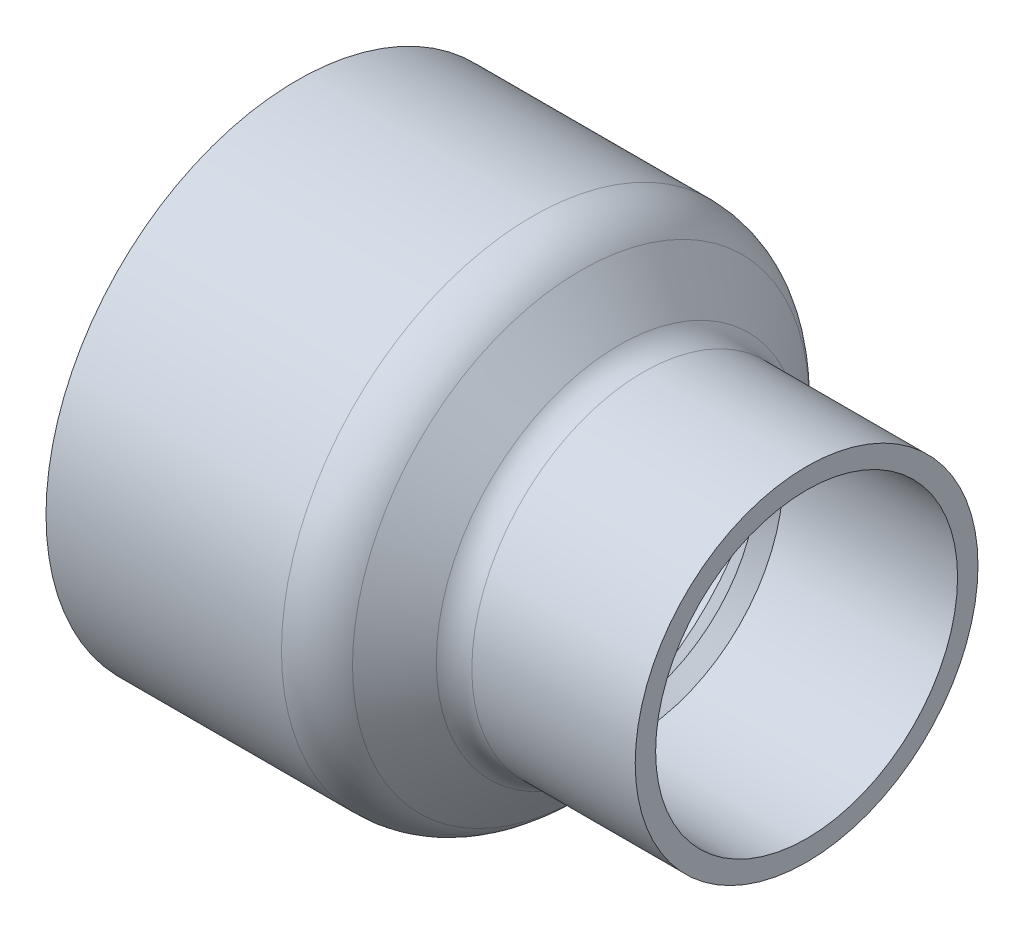
SolidWorks part; units mm, degrees
ref_plane "Front Plane" through (0, 0, 0) normal (0, 0, 1) x (1, 0, 0)
ref_plane "Top Plane" through (0, 0, 0) normal (0, 1, 0) x (1, 0, 0)
ref_plane "Right Plane" through (0, 0, 0) normal (1, 0, 0) x (0, 0, -1)
sketch "Sketch0" plane through (0, 0, 0) normal (0, 0, 1) x (1, 0, 0)
  line L0 (-51.181, 0) -> (16.383, 0) construction
  line L2 (-0.381, 0) -> (16.383, 0) construction
  line L3 (-51.181, 0) -> (51.181, 0) construction
  line L4 (-51.181, 50.3682) -> (-51.181, -50.3682) construction
  line L5 (-0.381, 44.3484) -> (-51.181, 44.6532) construction
  line L6 (-0.381, 44.3484) -> (-0.381, -44.3484) construction
  line L7 (-0.381, -44.3484) -> (-51.181, -44.6532) construction
  line L8 (-51.181, 44.6532) -> (-51.181, -44.6532) construction
  line L9 (51.181, 30.3149) -> (51.181, -30.3149) construction
  line L10 (51.181, 34.417) -> (51.181, -34.417) construction
  line L11 (16.383, 26.2509) -> (16.383, -26.2509) construction
  line L12 (16.383, 30.0863) -> (16.383, -30.0863) construction
  line L13 (16.383, -30.0863) -> (51.181, -30.3149) construction
  line L14 (-0.381, 38.9636) -> (-0.381, -38.9636) construction
  line L15 (16.383, 30.0863) -> (51.181, 30.3149) construction
  dimension "N" = 16.764
  dimension "M" = 100.7364
  dimension "OD A" = 89.3064
  dimension "OD B" = 88.6968
  dimension "ID" = 77.9272
  dimension "L" = 102.362
  dimension "ID2" = 52.5018
  dimension "OD B2" = 60.1726
  dimension "OD A2" = 60.6298
  dimension "M2" = 68.834
  dimension "C" = 50.8
  dimension "C2" = 34.798
sketch "Sketch1" plane through (0, 0, 0) normal (0, 0, 1) x (1, 0, 0)
  line L0 (-51.181, 0) -> (16.383, 0) construction
  line L1 (-51.181, 0) -> (16.383, 0) construction
  line L2 (-0.381, -44.3484) -> (13.5682, -27.7244)
  line L3 (0, -52.7853) -> (-4.3779, -49.1118) construction
  line L4 (-51.181, -50.3682) -> (-51.181, -44.6532)
  line L5 (-51.181, -44.6532) -> (-0.381, -44.3484)
  line L7 (13.5682, -27.7244) -> (16.383, -30.0863)
  line L8 (2.0282, -50.3682) -> (15.4128, -34.417)
  line L9 (2.0282, -50.3682) -> (-51.181, -50.3682)
  line L10 (0, 0) -> (0, -52.7853) construction
  line L12 (16.383, -30.0863) -> (51.181, -30.3149)
  line L13 (51.181, -30.3149) -> (51.181, -34.417)
  line L14 (51.181, -34.417) -> (15.4128, -34.417)
  dimension "D1" = 40
revolve "Revolve1" add sketch "Sketch1" angle 360 about L1
fillet "Fillet1" radius 12.7 1 edges at (2.0282, 0, 50.3682)
fillet "Fillet2" radius 6.35 1 edges at (15.4128, 0, 34.417)
other "CPoint1" parameters "Diameter"=50.8, "StubLength"=152.4
ref_axis "Axis1" through (26.383, 0, 0) along (-1, 0, 0)
other "CPoint2" parameters "Diameter"=76.2, "StubLength"=76.2
ref_axis "Axis2" through (-10.381, 0, 0) along (1, 0, 0)
other "RPoint1"
